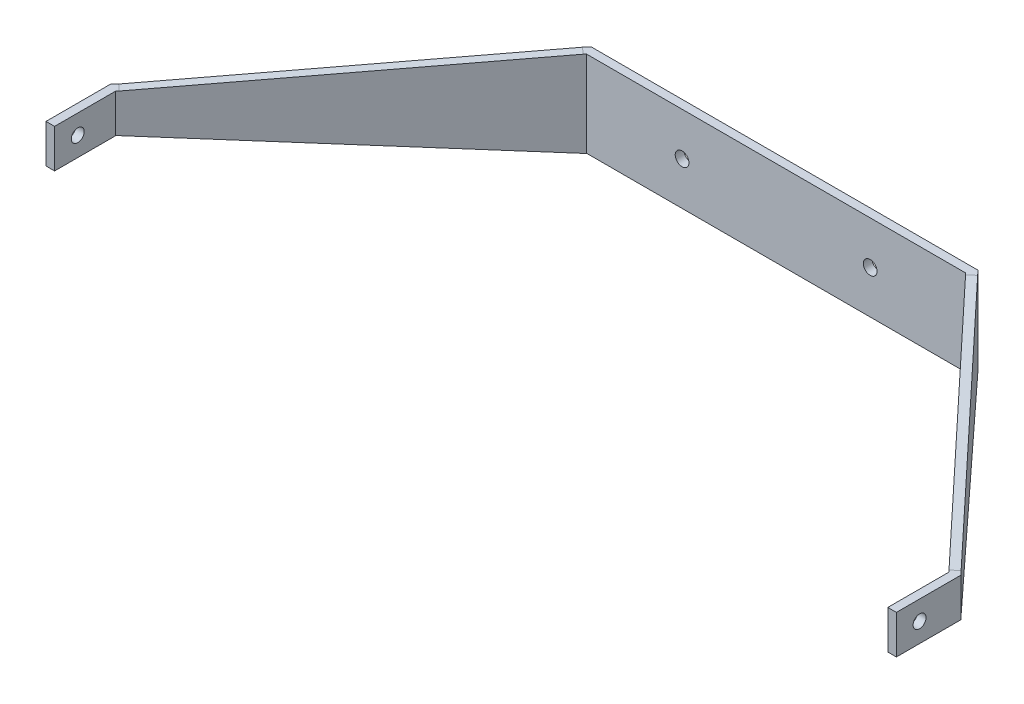
SolidWorks part; units mm, degrees
ref_plane "前视基准面" through (0, 0, 0) normal (0, 0, 1) x (1, 0, 0)
ref_plane "上视基准面" through (0, 0, 0) normal (0, 1, 0) x (1, 0, 0)
ref_plane "右视基准面" through (0, 0, 0) normal (1, 0, 0) x (0, 0, -1)
other "Configuration Table"
sketch "草图1" plane through (0, 0, 0) normal (0, 1, 0) x (1, 0, 0)
  line L0 (0, 0) -> (198, 0)
  line L1 (0, 0) -> (0, -73)
  line L2 (99, 0) -> (99, -78.112) construction
  line L3 (0, -73) -> (2, -73)
  line L4 (0, -73) -> (0, -58)
  line L5 (0, -58) -> (2, -58)
  line L6 (2, -73) -> (2, -58)
  line L7 (196, -73) -> (196, -58)
  line L8 (198, -58) -> (196, -58)
  line L9 (198, -73) -> (198, -58)
  line L10 (198, -73) -> (196, -73)
extrude "凸台-拉伸1" add sketch "草图1" along normal blind 9 contours L3 L6 L5 L1 | L10 L9 L8 L7 region at (1, 0, 65.5) region at (197, 0, 65.5)
sketch "草图2" plane through (198, 0, 0) normal (1, 0, 0) x (0, 0, -1)
  line L0 (-73, 4.5) -> (-58, 4.5) construction
  line L1 (-73, 9) -> (-73, 0) construction
  line L2 (-58, 9) -> (-58, 0) construction
  circle A0 centre (-67.6013, 4.5) radius 1.5
extrude "切除-拉伸1" cut sketch "草图2" against normal through all
ref_plane "基准面1" through (0, 0, 0) normal (0, 0, 1) x (1, 0, 0)
sketch "草图3" plane through (0, 0, 0) normal (0, 0, 1) x (1, 0, 0)
  line L0 (0, 0) -> (2, 0) construction
  line L1 (2, 0) -> (2, 9) construction
  line L2 (2, 9) -> (0, 9) construction
  line L3 (0, 9) -> (0, 0) construction
  line L4 (196, 0) -> (198, 0) construction
  line L5 (198, 0) -> (198, 9) construction
  line L6 (198, 9) -> (196, 9) construction
  line L7 (196, 9) -> (196, 0) construction
  line L8 (0, 0) -> (2, 0) construction
  line L9 (2, 0) -> (2, 9) construction
  line L10 (2, 9) -> (0, 9) construction
  line L11 (0, 9) -> (0, 0) construction
  line L12 (196, 0) -> (198, 0) construction
  line L13 (198, 0) -> (198, 9) construction
  line L14 (198, 9) -> (196, 9) construction
  line L15 (196, 9) -> (196, 0) construction
  line L16 (2, 4.5) -> (196, 4.5) construction
  line L17 (99, 4.5) -> (99, 40.5422) construction
  line L19 (54, 14.5) -> (144, 14.5)
  line L20 (54, 14.5) -> (54, -5.5)
  line L21 (54, -5.5) -> (144, -5.5)
  line L22 (144, 14.5) -> (144, -5.5)
  line L23 (54, 14.5) -> (144, -5.5) construction
  line L24 (54, -5.5) -> (144, 14.5) construction
extrude "凸台-拉伸2" add sketch "草图3" along normal blind 2 separate body
ref_plane "基准面2" through (77.1363, 0, -71.8166) normal (0.7319, 0, -0.6814) x (-0.6814, 0, -0.7319)
sketch "草图4" plane through (77.1363, 0, -71.8166) normal (0.7319, 0, -0.6814) x (-0.6814, 0, -0.7319)
  line L0 (-177.3707, 9) -> (-177.3707, 0) construction
  line L1 (-177.3707, 9) -> (-177.3707, 0)
  line L2 (-98.1243, -5.5) -> (-98.1243, 14.5) construction
  line L3 (-98.1243, -5.5) -> (-98.1243, 14.5)
  line L6 (-176.0079, 9) -> (-176.0079, 0) construction
  line L7 (-176.0079, 9) -> (-176.0079, 0)
  line L8 (-99.5881, -5.5) -> (-99.5881, 14.5) construction
  line L9 (-99.5881, -5.5) -> (-99.5881, 14.5)
  line L10 (-99.5881, -5.5) -> (-176.0079, 0)
  line L11 (-176.0079, 9) -> (-99.5881, 14.5)
  line L12 (-99.5881, 14.5) -> (-98.1243, 14.5)
  line L13 (-99.5881, -5.5) -> (-98.1243, -5.5)
  line L14 (-176.0079, 0) -> (-177.3707, 0)
  line L15 (-177.3707, 9) -> (-176.0079, 9)
extrude "凸台-拉伸3" add sketch "草图4" against normal blind 2 contours L15 L1 L14 L7 | L11 L7 L10 L9 | L9 L13 L3 L12 region at (197.5357, 4.5, 57.5013) region at (167.7424, 4.5, 25.5011) region at (144.4987, 4.5, 0.5357)
ref_plane "基准面3" through (99, 0, 0) normal (1, 0, 0) x (0, 0, -1)
mirror "镜向1" about plane through (99, 0, 0) normal (1, 0, 0) of "凸台-拉伸3"
combine bodies "组合1" operation type add bodies to combine 112 108
sketch "草图5" plane through (0, 0, 0) normal (0, 0, -1) x (-1, 0, 0)
  line L0 (-99, 14.5) -> (-99, -5.5) construction
  line L1 (-144, 14.5) -> (-54, 14.5) construction
  line L2 (-54, -5.5) -> (-144, -5.5) construction
sketch "草图6" plane through (0, 0, 0) normal (0, 0, -1) x (-1, 0, 0)
  line L0 (-99, 14.5) -> (-99, -5.5) construction
  line L1 (-99, 14.5) -> (-99, -5.5)
  line L2 (-99, 4.5) -> (-78.7, 4.5) construction
  line L3 (-78.7, 4.5) -> (-119.3, 4.5) construction
  line L4 (-78.7, 4.5) -> (-75.5, 4.5) construction
  line L5 (-119.3, 4.5) -> (-122.5, 4.5) construction
  circle A2 centre (-120.9, 4.5) radius 1.6
  circle A3 centre (-77.1, 4.5) radius 1.6
extrude "切除-拉伸2" cut sketch "草图6" against normal blind 10 contours A2 | A3 region at (120.9, 4.5, 0) region at (77.1, 4.5, 0)
